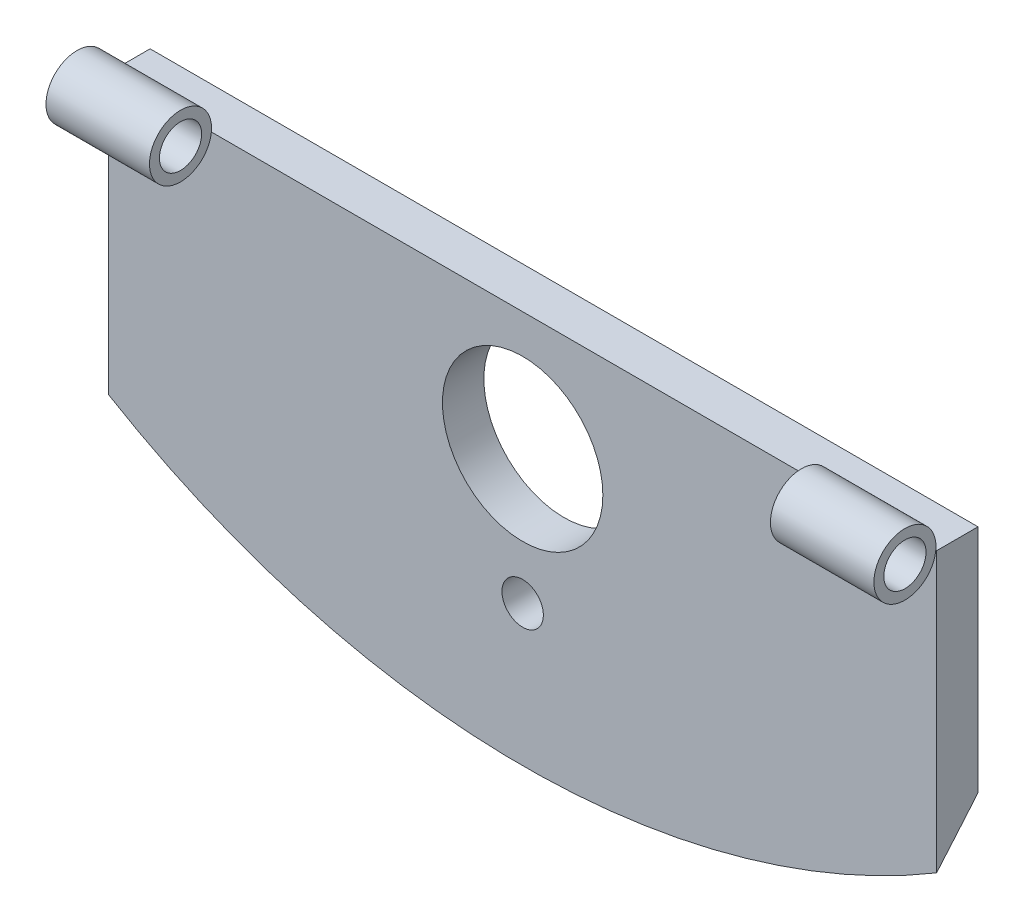
SolidWorks part; units mm, degrees
ref_plane "Front Plane" through (0, 0, 0) normal (0, 0, 1) x (1, 0, 0)
ref_plane "Top Plane" through (0, 0, 0) normal (0, 1, 0) x (1, 0, 0)
ref_plane "Right Plane" through (0, 0, 0) normal (1, 0, 0) x (0, 0, -1)
sketch "Sketch1" plane through (0, 0, 0) normal (0, 0, 1) x (1, 0, 0)
  line L9 (-80, 0) -> (-80, -53.9254)
  line L12 (80, 0) -> (80, -53.9254)
  line L13 (-80, 0) -> (80, 0)
  line L15 (80, 0) -> (80, -44.5151) construction
  line L16 (-80, 0) -> (-80, -44.5151) construction
  line L17 (-88, 8) -> (-88, -48.8099) construction
  line L18 (-88, 8) -> (88, 8) construction
  line L19 (88, 8) -> (88, -48.8099) construction
  arc A6 (-80, -53.9254) -> (80, -53.9254) centre (0, 80) ccw
  arc A8 (-88, -48.8099) -> (88, -48.8099) centre (0, 80) ccw construction
  arc A9 (-80, -44.5151) -> (80, -44.5151) centre (0, 80) ccw construction
  point P1 (0, 100)
  point P2 (-90, -40.6734)
  point P3 (90, -40.6734)
  point P6 (-80, 0)
  point P7 (80, -46.5913)
  point P8 (-80, -46.5913)
  point P10 (-80, -184.5757)
  point P11 (80, 0)
  point P12 (80, -184.5757)
  point P13 (80, 0)
  point P16 (-80, 0)
  dimension "D2" = 8
extrude "Boss-Extrude1" add sketch "Sketch1" along normal blind 8
sketch "Sketch2" plane through (0, 0, 8) normal (0, 0, 1) x (1, 0, 0)
  circle A0 centre (0, -22.9643) radius 15.5
  dimension "D1" = 31
extrude "Cut-Extrude1" cut sketch "Sketch2" against normal blind 8
chamfer "Chamfer1" distance 8 angle 45 1 edges at (0, -76, 0)
sketch "Sketch3" plane through (0, 0, 8) normal (0, 0, 1) x (1, 0, 0)
  circle A0 centre (0, -48.8066) radius 4
  dimension "D1" = 8
extrude "Cut-Extrude2" cut sketch "Sketch3" against normal blind 60
sketch "Sketch4" plane through (-80, 0, 0) normal (-1, 0, 0) x (0, 0, 1)
  circle A0 centre (14.1224, 0.7821) radius 4.08
  circle A1 centre (14.1224, 0.7821) radius 6
extrude "Boss-Extrude2" add sketch "Sketch4" against normal blind 20 separate body
sketch "Sketch5" plane through (80, 0, 0) normal (1, 0, 0) x (0, 0, -1)
  circle A0 centre (-14.1224, 0.7821) radius 4.08
  circle A1 centre (-14.1224, 0.7821) radius 6
extrude "Boss-Extrude3" add sketch "Sketch5" against normal blind 20 separate body
